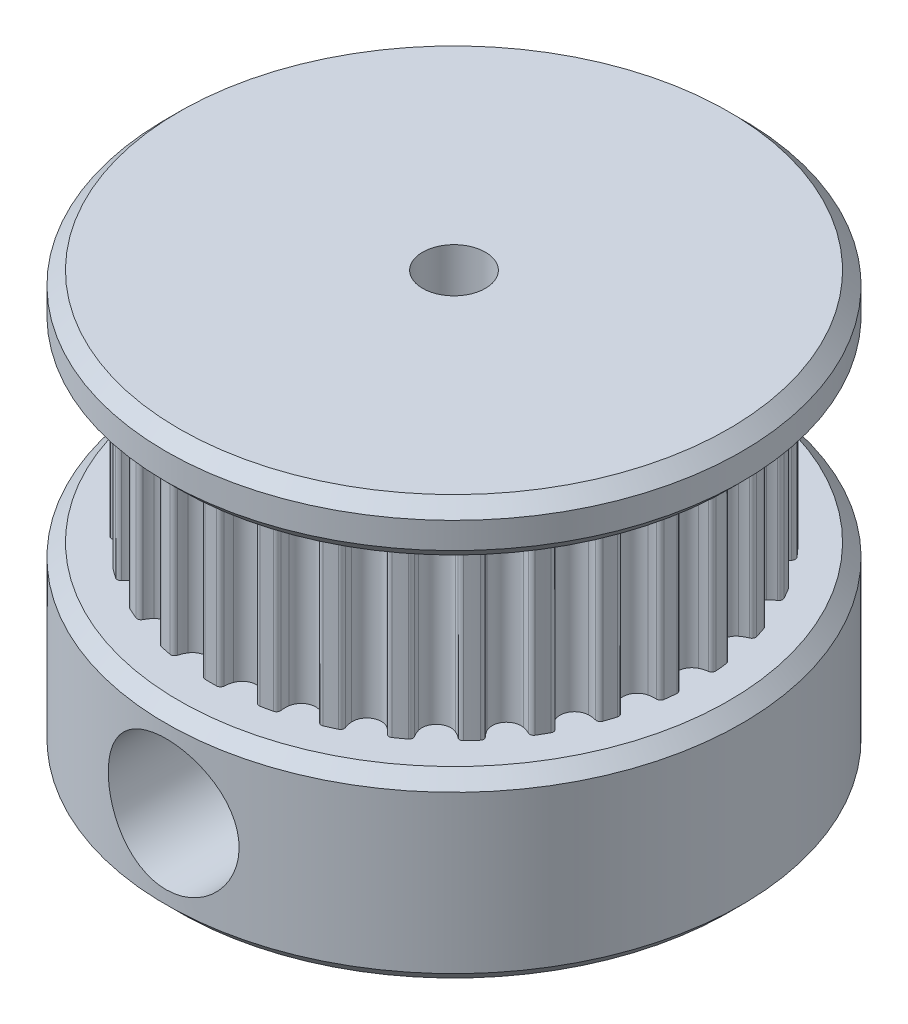
SolidWorks part; units mm, degrees
other "Markup1"
sketch "Sketch11" plane through (-10, 5.5, 10) normal (-0.2341, 0.0958, 0.9675) x (0.972, 0, 0.2351)
sketch "Sketch12" plane through (-9.5, 5.5, 9.5) normal (-0.2341, 0.0958, 0.9675) x (0.972, 0, 0.2351)
sketch "Sketch13" plane through (-9.5, 5.5, 9.5) normal (-0.2341, 0.0958, 0.9675) x (0.972, 0, 0.2351)
sketch "Sketch15" plane through (-15, 5.5, 15) normal (-0.2341, 0.0958, 0.9675) x (0.972, 0, 0.2351)
sketch "Sketch16" plane through (-15, 5.5, 15) normal (-0.2341, 0.0958, 0.9675) x (0.972, 0, 0.2351)
sketch "Sketch17" plane through (-15, 5.5, 15) normal (-0.2341, 0.0958, 0.9675) x (0.972, 0, 0.2351)
ref_plane "Front Plane" through (0, 0, 0) normal (0, 0, 1) x (1, 0, 0)
ref_plane "Top Plane" through (0, 0, 0) normal (0, 1, 0) x (1, 0, 0)
ref_plane "Right Plane" through (0, 0, 0) normal (1, 0, 0) x (0, 0, -1)
sketch "Sketch1" plane through (0, 0, 0) normal (0, 1, 0) x (1, 0, 0)
  line L0 (0, 0) -> (0, 9.5493) construction
  line L2 (0, 0) -> (0.9503, 9.0419) construction
  line L3 (0, 0) -> (1.4059, 9.4452) construction
  line L4 (1.3685, 9.194) -> (0.9767, 5.4662) construction
  circle A0 centre (0, 0) radius 9.5493
  arc A1 (0.4288, 8.8522) -> (0.8923, 8.4899) centre (0.9503, 9.0419) ccw
  arc A2 (0.3695, 9.1494) -> (0.2233, 9.2926) centre (0.2197, 9.1427) ccw
  arc A3 (0.3695, 9.1494) -> (0.4288, 8.8522) centre (1.3685, 9.194) ccw
  arc A4 (-0.4288, 8.8522) -> (-0.8923, 8.4899) centre (-0.9503, 9.0419) cw
  arc A5 (0.2233, 9.2926) -> (-0.2233, 9.2926) centre (0, 0) ccw
  arc A6 (-0.3695, 9.1494) -> (-0.4288, 8.8522) centre (-1.3685, 9.194) cw
  arc A7 (-0.3695, 9.1494) -> (-0.2233, 9.2926) centre (-0.2197, 9.1427) cw
  arc A8 (1.4211, 8.7479) -> (0.8923, 8.4899) centre (0.9503, 9.0419) cw
  arc A9 (1.5408, 9.0262) -> (1.4211, 8.7479) centre (0.5729, 9.2776) cw
  arc A10 (1.5408, 9.0262) -> (1.7136, 9.136) centre (1.686, 8.9885) cw
  arc A11 (2.1504, 9.0431) -> (1.7136, 9.136) centre (0, 0) ccw
  arc A12 (2.2637, 8.8726) -> (2.1504, 9.0431) centre (2.1157, 8.8972) ccw
  arc A13 (2.2637, 8.8726) -> (2.2599, 8.5696) centre (3.2502, 8.7086) ccw
  arc A14 (2.2599, 8.5696) -> (2.638, 8.1189) centre (2.8095, 8.6467) ccw
  arc A15 (3.2088, 8.2612) -> (2.638, 8.1189) centre (2.8095, 8.6467) cw
  arc A16 (3.3838, 8.5087) -> (3.2088, 8.2612) centre (2.4893, 8.9558) cw
  arc A17 (3.3838, 8.5087) -> (3.5757, 8.58) centre (3.518, 8.4416) cw
  arc A18 (3.9836, 8.3984) -> (3.5757, 8.58) centre (0, 0) ccw
  arc A19 (4.059, 8.2081) -> (3.9836, 8.3984) centre (3.9193, 8.2629) ccw
  arc A20 (4.059, 8.2081) -> (3.9922, 7.9124) centre (4.9898, 7.8425) ccw
  arc A21 (3.9922, 7.9124) -> (4.2683, 7.393) centre (4.5458, 7.8736) ccw
  arc A22 (4.8563, 7.4136) -> (4.2683, 7.393) centre (4.5458, 7.8736) cw
  arc A23 (5.0789, 7.6192) -> (4.8563, 7.4136) centre (4.2969, 8.2425) cw
  arc A24 (5.0789, 7.6192) -> (5.2814, 7.6491) centre (5.1962, 7.5257) cw
  arc A25 (5.6427, 7.3866) -> (5.2814, 7.6491) centre (0, 0) ccw
  arc A26 (5.6768, 7.1848) -> (5.6427, 7.3866) centre (5.5516, 7.2674) ccw
  arc A27 (5.6768, 7.1848) -> (5.5501, 6.9095) centre (6.5113, 6.6337) ccw
  arc A28 (5.5501, 6.9095) -> (5.7122, 6.344) centre (6.0835, 6.7564) ccw
  arc A29 (6.2915, 6.2419) -> (5.7122, 6.344) centre (6.0835, 6.7564) cw
  arc A30 (6.552, 6.3967) -> (6.2915, 6.2419) centre (5.9167, 7.169) cw
  arc A31 (6.552, 6.3967) -> (6.7564, 6.3839) centre (6.6473, 6.2809) cw
  arc A32 (7.0552, 6.052) -> (6.7564, 6.3839) centre (0, 0) ccw
  arc A33 (7.0466, 5.8475) -> (7.0552, 6.052) centre (6.9413, 5.9544) ccw
  arc A34 (7.0466, 5.8475) -> (6.8653, 5.6046) centre (7.7482, 5.135) ccw
  arc A35 (6.8653, 5.6046) -> (6.9063, 5.0177) centre (7.3553, 5.344) ccw
  arc A36 (7.4518, 4.7974) -> (6.9063, 5.0177) centre (7.3553, 5.344) cw
  arc A37 (7.7388, 4.8947) -> (7.4518, 4.7974) centre (7.278, 5.7822) cw
  arc A38 (7.7388, 4.8947) -> (7.936, 4.8397) centre (7.8079, 4.7616) cw
  arc A39 (8.1593, 4.4529) -> (7.936, 4.8397) centre (0, 0) ccw
  arc A40 (8.1083, 4.2547) -> (8.1593, 4.4529) centre (8.0276, 4.3811) ccw
  arc A41 (8.1083, 4.2547) -> (7.8806, 4.0547) centre (8.6465, 3.4118) ccw
  arc A42 (7.8806, 4.0547) -> (7.7987, 3.4722) centre (8.3057, 3.6979) ccw
  arc A43 (8.2864, 3.1433) -> (7.7987, 3.4722) centre (8.3057, 3.6979) cw
  arc A44 (8.5874, 3.1787) -> (8.2864, 3.1433) centre (8.3211, 4.1427) cw
  arc A45 (8.5874, 3.1787) -> (8.7688, 3.0839) centre (8.6273, 3.0342) cw
  arc A46 (8.9068, 2.6592) -> (8.7688, 3.0839) centre (0, 0) ccw
  arc A47 (8.8157, 2.4759) -> (8.9068, 2.6592) centre (8.7631, 2.6163) ccw
  arc A48 (8.8157, 2.4759) -> (8.5514, 2.3277) centre (9.1669, 1.5396) ccw
  arc A49 (8.5514, 2.3277) -> (8.3501, 1.7749) centre (8.893, 1.8903) ccw
  arc A50 (8.7588, 1.3517) -> (8.3501, 1.7749) centre (8.893, 1.8903) cw
  arc A51 (9.0606, 1.3239) -> (8.7588, 1.3517) centre (9.0006, 2.3221) cw
  arc A52 (9.0606, 1.3239) -> (9.2184, 1.1934) centre (9.0696, 1.1741) cw
  arc A53 (9.265, 0.7493) -> (9.2184, 1.1934) centre (0, 0) ccw
  arc A54 (9.1379, 0.5889) -> (9.265, 0.7493) centre (9.1155, 0.7372) ccw
  arc A55 (9.1379, 0.5889) -> (8.8485, 0.4989) centre (9.2867, -0.4) ccw
  arc A56 (8.8485, 0.4989) -> (8.5367, 0) centre (9.0917, 0) ccw
  arc A57 (8.8485, -0.4989) -> (8.5367, 0) centre (9.0917, 0) cw
  arc A58 (9.1379, -0.5889) -> (8.8485, -0.4989) centre (9.2867, 0.4) cw
  arc A59 (9.1379, -0.5889) -> (9.265, -0.7493) centre (9.1155, -0.7372) cw
  arc A60 (9.2184, -1.1934) -> (9.265, -0.7493) centre (0, 0) ccw
  arc A61 (9.0606, -1.3239) -> (9.2184, -1.1934) centre (9.0696, -1.1741) ccw
  arc A62 (9.0606, -1.3239) -> (8.7588, -1.3517) centre (9.0006, -2.3221) ccw
  arc A63 (8.7588, -1.3517) -> (8.3501, -1.7749) centre (8.893, -1.8903) ccw
  arc A64 (8.5514, -2.3277) -> (8.3501, -1.7749) centre (8.893, -1.8903) cw
  arc A65 (8.8157, -2.4759) -> (8.5514, -2.3277) centre (9.1669, -1.5396) cw
  arc A66 (8.8157, -2.4759) -> (8.9068, -2.6592) centre (8.7631, -2.6163) cw
  arc A67 (8.7688, -3.0839) -> (8.9068, -2.6592) centre (0, 0) ccw
  arc A68 (8.5874, -3.1787) -> (8.7688, -3.0839) centre (8.6273, -3.0342) ccw
  arc A69 (8.5874, -3.1787) -> (8.2864, -3.1433) centre (8.3211, -4.1427) ccw
  arc A70 (8.2864, -3.1433) -> (7.7987, -3.4722) centre (8.3057, -3.6979) ccw
  arc A71 (7.8806, -4.0547) -> (7.7987, -3.4722) centre (8.3057, -3.6979) cw
  arc A72 (8.1083, -4.2547) -> (7.8806, -4.0547) centre (8.6465, -3.4118) cw
  arc A73 (8.1083, -4.2547) -> (8.1593, -4.4529) centre (8.0276, -4.3811) cw
  arc A74 (7.936, -4.8397) -> (8.1593, -4.4529) centre (0, 0) ccw
  arc A75 (7.7388, -4.8947) -> (7.936, -4.8397) centre (7.8079, -4.7616) ccw
  arc A76 (7.7388, -4.8947) -> (7.4518, -4.7974) centre (7.278, -5.7822) ccw
  arc A77 (7.4518, -4.7974) -> (6.9063, -5.0177) centre (7.3553, -5.344) ccw
  arc A78 (6.8653, -5.6046) -> (6.9063, -5.0177) centre (7.3553, -5.344) cw
  arc A79 (7.0466, -5.8475) -> (6.8653, -5.6046) centre (7.7482, -5.135) cw
  arc A80 (7.0466, -5.8475) -> (7.0552, -6.052) centre (6.9413, -5.9544) cw
  arc A81 (6.7564, -6.3839) -> (7.0552, -6.052) centre (0, 0) ccw
  arc A82 (6.552, -6.3967) -> (6.7564, -6.3839) centre (6.6473, -6.2809) ccw
  arc A83 (6.552, -6.3967) -> (6.2915, -6.2419) centre (5.9167, -7.169) ccw
  arc A84 (6.2915, -6.2419) -> (5.7122, -6.344) centre (6.0835, -6.7564) ccw
  arc A85 (5.5501, -6.9095) -> (5.7122, -6.344) centre (6.0835, -6.7564) cw
  arc A86 (5.6768, -7.1848) -> (5.5501, -6.9095) centre (6.5113, -6.6337) cw
  arc A87 (5.6768, -7.1848) -> (5.6427, -7.3866) centre (5.5516, -7.2674) cw
  arc A88 (5.2814, -7.6491) -> (5.6427, -7.3866) centre (0, 0) ccw
  arc A89 (5.0789, -7.6192) -> (5.2814, -7.6491) centre (5.1962, -7.5257) ccw
  arc A90 (5.0789, -7.6192) -> (4.8563, -7.4136) centre (4.2969, -8.2425) ccw
  arc A91 (4.8563, -7.4136) -> (4.2683, -7.393) centre (4.5458, -7.8736) ccw
  arc A92 (3.9922, -7.9124) -> (4.2683, -7.393) centre (4.5458, -7.8736) cw
  arc A93 (4.059, -8.2081) -> (3.9922, -7.9124) centre (4.9898, -7.8425) cw
  arc A94 (4.059, -8.2081) -> (3.9836, -8.3984) centre (3.9193, -8.2629) cw
  arc A95 (3.5757, -8.58) -> (3.9836, -8.3984) centre (0, 0) ccw
  arc A96 (3.3838, -8.5087) -> (3.5757, -8.58) centre (3.518, -8.4416) ccw
  arc A97 (3.3838, -8.5087) -> (3.2088, -8.2612) centre (2.4893, -8.9558) ccw
  arc A98 (3.2088, -8.2612) -> (2.638, -8.1189) centre (2.8095, -8.6467) ccw
  arc A99 (2.2599, -8.5696) -> (2.638, -8.1189) centre (2.8095, -8.6467) cw
  arc A100 (2.2637, -8.8726) -> (2.2599, -8.5696) centre (3.2502, -8.7086) cw
  arc A101 (2.2637, -8.8726) -> (2.1504, -9.0431) centre (2.1157, -8.8972) cw
  arc A102 (1.7136, -9.136) -> (2.1504, -9.0431) centre (0, 0) ccw
  arc A103 (1.5408, -9.0262) -> (1.7136, -9.136) centre (1.686, -8.9885) ccw
  arc A104 (1.5408, -9.0262) -> (1.4211, -8.7479) centre (0.5729, -9.2776) ccw
  arc A105 (1.4211, -8.7479) -> (0.8923, -8.4899) centre (0.9503, -9.0419) ccw
  arc A106 (0.4288, -8.8522) -> (0.8923, -8.4899) centre (0.9503, -9.0419) cw
  arc A107 (0.3695, -9.1494) -> (0.4288, -8.8522) centre (1.3685, -9.194) cw
  arc A108 (0.3695, -9.1494) -> (0.2233, -9.2926) centre (0.2197, -9.1427) cw
  arc A109 (-0.2233, -9.2926) -> (0.2233, -9.2926) centre (0, 0) ccw
  arc A110 (-0.3695, -9.1494) -> (-0.2233, -9.2926) centre (-0.2197, -9.1427) ccw
  arc A111 (-0.3695, -9.1494) -> (-0.4288, -8.8522) centre (-1.3685, -9.194) ccw
  arc A112 (-0.4288, -8.8522) -> (-0.8923, -8.4899) centre (-0.9503, -9.0419) ccw
  arc A113 (-1.4211, -8.7479) -> (-0.8923, -8.4899) centre (-0.9503, -9.0419) cw
  arc A114 (-1.5408, -9.0262) -> (-1.4211, -8.7479) centre (-0.5729, -9.2776) cw
  arc A115 (-1.5408, -9.0262) -> (-1.7136, -9.136) centre (-1.686, -8.9885) cw
  arc A116 (-2.1504, -9.0431) -> (-1.7136, -9.136) centre (0, 0) ccw
  arc A117 (-2.2637, -8.8726) -> (-2.1504, -9.0431) centre (-2.1157, -8.8972) ccw
  arc A118 (-2.2637, -8.8726) -> (-2.2599, -8.5696) centre (-3.2502, -8.7086) ccw
  arc A119 (-2.2599, -8.5696) -> (-2.638, -8.1189) centre (-2.8095, -8.6467) ccw
  arc A120 (-3.2088, -8.2612) -> (-2.638, -8.1189) centre (-2.8095, -8.6467) cw
  arc A121 (-3.3838, -8.5087) -> (-3.2088, -8.2612) centre (-2.4893, -8.9558) cw
  arc A122 (-3.3838, -8.5087) -> (-3.5757, -8.58) centre (-3.518, -8.4416) cw
  arc A123 (-3.9836, -8.3984) -> (-3.5757, -8.58) centre (0, 0) ccw
  arc A124 (-4.059, -8.2081) -> (-3.9836, -8.3984) centre (-3.9193, -8.2629) ccw
  arc A125 (-4.059, -8.2081) -> (-3.9922, -7.9124) centre (-4.9898, -7.8425) ccw
  arc A126 (-3.9922, -7.9124) -> (-4.2683, -7.393) centre (-4.5458, -7.8736) ccw
  arc A127 (-4.8563, -7.4136) -> (-4.2683, -7.393) centre (-4.5458, -7.8736) cw
  arc A128 (-5.0789, -7.6192) -> (-4.8563, -7.4136) centre (-4.2969, -8.2425) cw
  arc A129 (-5.0789, -7.6192) -> (-5.2814, -7.6491) centre (-5.1962, -7.5257) cw
  arc A130 (-5.6427, -7.3866) -> (-5.2814, -7.6491) centre (0, 0) ccw
  arc A131 (-5.6768, -7.1848) -> (-5.6427, -7.3866) centre (-5.5516, -7.2674) ccw
  arc A132 (-5.6768, -7.1848) -> (-5.5501, -6.9095) centre (-6.5113, -6.6337) ccw
  arc A133 (-5.5501, -6.9095) -> (-5.7122, -6.344) centre (-6.0835, -6.7564) ccw
  arc A134 (-6.2915, -6.2419) -> (-5.7122, -6.344) centre (-6.0835, -6.7564) cw
  arc A135 (-6.552, -6.3967) -> (-6.2915, -6.2419) centre (-5.9167, -7.169) cw
  arc A136 (-6.552, -6.3967) -> (-6.7564, -6.3839) centre (-6.6473, -6.2809) cw
  arc A137 (-7.0552, -6.052) -> (-6.7564, -6.3839) centre (0, 0) ccw
  arc A138 (-7.0466, -5.8475) -> (-7.0552, -6.052) centre (-6.9413, -5.9544) ccw
  arc A139 (-7.0466, -5.8475) -> (-6.8653, -5.6046) centre (-7.7482, -5.135) ccw
  arc A140 (-6.8653, -5.6046) -> (-6.9063, -5.0177) centre (-7.3553, -5.344) ccw
  arc A141 (-7.4518, -4.7974) -> (-6.9063, -5.0177) centre (-7.3553, -5.344) cw
  arc A142 (-7.7388, -4.8947) -> (-7.4518, -4.7974) centre (-7.278, -5.7822) cw
  arc A143 (-7.7388, -4.8947) -> (-7.936, -4.8397) centre (-7.8079, -4.7616) cw
  arc A144 (-8.1593, -4.4529) -> (-7.936, -4.8397) centre (0, 0) ccw
  arc A145 (-8.1083, -4.2547) -> (-8.1593, -4.4529) centre (-8.0276, -4.3811) ccw
  arc A146 (-8.1083, -4.2547) -> (-7.8806, -4.0547) centre (-8.6465, -3.4118) ccw
  arc A147 (-7.8806, -4.0547) -> (-7.7987, -3.4722) centre (-8.3057, -3.6979) ccw
  arc A148 (-8.2864, -3.1433) -> (-7.7987, -3.4722) centre (-8.3057, -3.6979) cw
  arc A149 (-8.5874, -3.1787) -> (-8.2864, -3.1433) centre (-8.3211, -4.1427) cw
  arc A150 (-8.5874, -3.1787) -> (-8.7688, -3.0839) centre (-8.6273, -3.0342) cw
  arc A151 (-8.9068, -2.6592) -> (-8.7688, -3.0839) centre (0, 0) ccw
  arc A152 (-8.8157, -2.4759) -> (-8.9068, -2.6592) centre (-8.7631, -2.6163) ccw
  arc A153 (-8.8157, -2.4759) -> (-8.5514, -2.3277) centre (-9.1669, -1.5396) ccw
  arc A154 (-8.5514, -2.3277) -> (-8.3501, -1.7749) centre (-8.893, -1.8903) ccw
  arc A155 (-8.7588, -1.3517) -> (-8.3501, -1.7749) centre (-8.893, -1.8903) cw
  arc A156 (-9.0606, -1.3239) -> (-8.7588, -1.3517) centre (-9.0006, -2.3221) cw
  arc A157 (-9.0606, -1.3239) -> (-9.2184, -1.1934) centre (-9.0696, -1.1741) cw
  arc A158 (-9.265, -0.7493) -> (-9.2184, -1.1934) centre (0, 0) ccw
  arc A159 (-9.1379, -0.5889) -> (-9.265, -0.7493) centre (-9.1155, -0.7372) ccw
  arc A160 (-9.1379, -0.5889) -> (-8.8485, -0.4989) centre (-9.2867, 0.4) ccw
  arc A161 (-8.8485, -0.4989) -> (-8.5367, 0) centre (-9.0917, 0) ccw
  arc A162 (-8.8485, 0.4989) -> (-8.5367, 0) centre (-9.0917, 0) cw
  arc A163 (-9.1379, 0.5889) -> (-8.8485, 0.4989) centre (-9.2867, -0.4) cw
  arc A164 (-9.1379, 0.5889) -> (-9.265, 0.7493) centre (-9.1155, 0.7372) cw
  arc A165 (-9.2184, 1.1934) -> (-9.265, 0.7493) centre (0, 0) ccw
  arc A166 (-9.0606, 1.3239) -> (-9.2184, 1.1934) centre (-9.0696, 1.1741) ccw
  arc A167 (-9.0606, 1.3239) -> (-8.7588, 1.3517) centre (-9.0006, 2.3221) ccw
  arc A168 (-8.7588, 1.3517) -> (-8.3501, 1.7749) centre (-8.893, 1.8903) ccw
  arc A169 (-8.5514, 2.3277) -> (-8.3501, 1.7749) centre (-8.893, 1.8903) cw
  arc A170 (-8.8157, 2.4759) -> (-8.5514, 2.3277) centre (-9.1669, 1.5396) cw
  arc A171 (-8.8157, 2.4759) -> (-8.9068, 2.6592) centre (-8.7631, 2.6163) cw
  arc A172 (-8.7688, 3.0839) -> (-8.9068, 2.6592) centre (0, 0) ccw
  arc A173 (-8.5874, 3.1787) -> (-8.7688, 3.0839) centre (-8.6273, 3.0342) ccw
  arc A174 (-8.5874, 3.1787) -> (-8.2864, 3.1433) centre (-8.3211, 4.1427) ccw
  arc A175 (-8.2864, 3.1433) -> (-7.7987, 3.4722) centre (-8.3057, 3.6979) ccw
  arc A176 (-7.8806, 4.0547) -> (-7.7987, 3.4722) centre (-8.3057, 3.6979) cw
  arc A177 (-8.1083, 4.2547) -> (-7.8806, 4.0547) centre (-8.6465, 3.4118) cw
  arc A178 (-8.1083, 4.2547) -> (-8.1593, 4.4529) centre (-8.0276, 4.3811) cw
  arc A179 (-7.936, 4.8397) -> (-8.1593, 4.4529) centre (0, 0) ccw
  arc A180 (-7.7388, 4.8947) -> (-7.936, 4.8397) centre (-7.8079, 4.7616) ccw
  arc A181 (-7.7388, 4.8947) -> (-7.4518, 4.7974) centre (-7.278, 5.7822) ccw
  arc A182 (-7.4518, 4.7974) -> (-6.9063, 5.0177) centre (-7.3553, 5.344) ccw
  arc A183 (-6.8653, 5.6046) -> (-6.9063, 5.0177) centre (-7.3553, 5.344) cw
  arc A184 (-7.0466, 5.8475) -> (-6.8653, 5.6046) centre (-7.7482, 5.135) cw
  arc A185 (-7.0466, 5.8475) -> (-7.0552, 6.052) centre (-6.9413, 5.9544) cw
  arc A186 (-6.7564, 6.3839) -> (-7.0552, 6.052) centre (0, 0) ccw
  arc A187 (-6.552, 6.3967) -> (-6.7564, 6.3839) centre (-6.6473, 6.2809) ccw
  arc A188 (-6.552, 6.3967) -> (-6.2915, 6.2419) centre (-5.9167, 7.169) ccw
  arc A189 (-6.2915, 6.2419) -> (-5.7122, 6.344) centre (-6.0835, 6.7564) ccw
  arc A190 (-5.5501, 6.9095) -> (-5.7122, 6.344) centre (-6.0835, 6.7564) cw
  arc A191 (-5.6768, 7.1848) -> (-5.5501, 6.9095) centre (-6.5113, 6.6337) cw
  arc A192 (-5.6768, 7.1848) -> (-5.6427, 7.3866) centre (-5.5516, 7.2674) cw
  arc A193 (-5.2814, 7.6491) -> (-5.6427, 7.3866) centre (0, 0) ccw
  arc A194 (-5.0789, 7.6192) -> (-5.2814, 7.6491) centre (-5.1962, 7.5257) ccw
  arc A195 (-5.0789, 7.6192) -> (-4.8563, 7.4136) centre (-4.2969, 8.2425) ccw
  arc A196 (-4.8563, 7.4136) -> (-4.2683, 7.393) centre (-4.5458, 7.8736) ccw
  arc A197 (-3.9922, 7.9124) -> (-4.2683, 7.393) centre (-4.5458, 7.8736) cw
  arc A198 (-4.059, 8.2081) -> (-3.9922, 7.9124) centre (-4.9898, 7.8425) cw
  arc A199 (-4.059, 8.2081) -> (-3.9836, 8.3984) centre (-3.9193, 8.2629) cw
  arc A200 (-3.5757, 8.58) -> (-3.9836, 8.3984) centre (0, 0) ccw
  arc A201 (-3.3838, 8.5087) -> (-3.5757, 8.58) centre (-3.518, 8.4416) ccw
  arc A202 (-3.3838, 8.5087) -> (-3.2088, 8.2612) centre (-2.4893, 8.9558) ccw
  arc A203 (-3.2088, 8.2612) -> (-2.638, 8.1189) centre (-2.8095, 8.6467) ccw
  arc A204 (-2.2599, 8.5696) -> (-2.638, 8.1189) centre (-2.8095, 8.6467) cw
  arc A205 (-2.2637, 8.8726) -> (-2.2599, 8.5696) centre (-3.2502, 8.7086) cw
  arc A206 (-2.2637, 8.8726) -> (-2.1504, 9.0431) centre (-2.1157, 8.8972) cw
  arc A207 (-1.7136, 9.136) -> (-2.1504, 9.0431) centre (0, 0) ccw
  arc A208 (-1.5408, 9.0262) -> (-1.7136, 9.136) centre (-1.686, 8.9885) ccw
  arc A209 (-1.5408, 9.0262) -> (-1.4211, 8.7479) centre (-0.5729, 9.2776) ccw
  arc A210 (-1.4211, 8.7479) -> (-0.8923, 8.4899) centre (-0.9503, 9.0419) ccw
  point P4 (0, 9.2953)
  point P11 (0, 9.5493)
  point P67 (0, 0)
  dimension "D1" = 19.0986
  dimension "D3" = 1
  dimension "D4" = 0.555
  dimension "D2" = 0.15
  dimension "D5" = 0.4
  dimension "D8" = 0.254
  dimension "D7" = 6
  dimension "D6" = 0.254
  dimension "D9" = 30
extrude "Gear" add sketch "Sketch1" along normal mid plane 7 contours A140 A139 A138 A137 A136 A135 A134 A133 A132 A131 A130 A129 A128 A127 A126 A125 A124 A123 A122 A121 A120 A119 A118 A117 A116 A115 A114 A113 A112 A111 A110 A109 A108 A107 A106 A105 A104 A103 A102 A101 A100 A99 A98 A97 A96 A95 A94 A93 A92 A91 A90 region at (0, 0, 0)
sketch "Sketch2" plane through (0, -3.5, 0) normal (0, -1, 0) x (1, 0, 0)
  circle A4 centre (0, 0) radius 11
  circle A5 centre (0, 0) radius 1.2
  point P4 (0, 0)
  dimension "D4" = 22
  dimension "D5" = 2.4
extrude "Base" add sketch "Sketch2" along normal blind 7 contours A4 A5 region at (-10.6889, -3.5, 0)
sketch "Sketch3" plane through (0, 0, 0) normal (0, 0, 1) x (1, 0, 0)
  line L0 (0, 0) -> (0, -7) construction
  line L1 (0, -10.06) -> (2.65, -8.53)
  line L2 (2.65, -8.53) -> (2.65, -5.47)
  line L3 (2.65, -5.47) -> (0, -3.94)
  line L4 (0, -3.94) -> (-2.65, -5.47)
  line L5 (-2.65, -5.47) -> (-2.65, -8.53)
  line L6 (-2.65, -8.53) -> (0, -10.06)
  line L7 (-2.65, -8.53) -> (-2.65, -10.5)
  line L9 (-11, -10.5) -> (11, -10.5) construction
  line L10 (-2.65, -10.5) -> (2.65, -10.5)
  line L11 (2.65, -10.5) -> (2.65, -8.53)
  circle A0 centre (0, -7) radius 2.65 construction
  dimension "D1" = 5.3
  dimension "D2" = 7
extrude "Nut Passthrough" cut sketch "Sketch3" along normal blind 3.35 contours L1 L6 | L5 L6 L1 L2 L3 L4 region at (0, -7, 0) region at (1.3533, -9.3439, 0)
sketch "Sketch9" plane through (0, 3.5, 0) normal (0, 1, 0) x (1, 0, 0)
  circle A0 centre (0, 0) radius 11
  dimension "D1" = 22
extrude "Top" add sketch "Sketch9" along normal blind 2
extrude "Shaft Hole" cut sketch "Sketch2<4>" against normal through all contours A5 | A5 region at (0, -3.5, 0)
sketch "Sketch2<4>" plane through (0, -3.5, 0) normal (0, -1, 0) x (1, 0, 0) same geometry as "Sketch2"
sketch "Sketch10" plane through (0, 0, 0) normal (0, 0, 1) x (1, 0, 0)
  circle A0 centre (0, -7) radius 1.4
  circle A1 centre (0, -7) radius 2.5
  dimension "D1" = 2.8
  dimension "D2" = 5
extrude "Screw Hole" cut sketch "Sketch10" along normal through all contours A0 region at (0, -7, 0)
extrude "Screw Counterbore" cut sketch "Sketch10<3>" along normal through all from offset 4.65
sketch "Sketch10<3>" plane through (0, 0, 0) normal (0, 0, 1) x (1, 0, 0) same geometry as "Sketch10"
chamfer "Chamfer2" distance 1.1 angle 45 1 edges at (2.5, -7, 4.65)
sketch "Sketch14" plane through (0, 0, 0) normal (0, 1, 0) x (1, 0, 0)
  circle A0 centre (0, 0) radius 1
  dimension "D1" = 2
extrude "Boss-Extrude1" add sketch "Sketch14" against normal up to surface (10.5 mm away) separate body up to face at (0, -10.5, -11)
chamfer "Chamfer3" distance 0.5 angle 45 4 edges at (0, 5.5, 11) (0, 3.5, 11) (0, -10.5, -11) (0, -3.5, -11)
equation "\"D1@Sketch1\"=\"pd\""
equation "\"teethNum\"= 30"
equation "\"pitch\"= 2mm"
equation "\"pd\"= \"teethNum\" * \"pitch\" / PI"
equation "\"D9@Sketch1\"=\"teethNum\""
equation "\"outerDia\" = 22"
equation "\"D4@Sketch2\"=\"outerDia\""
equation "\"D1@Sketch9\"=\"outerDia\""
equation "\"D7@Sketch1\"=180/ \"teethNum\""
